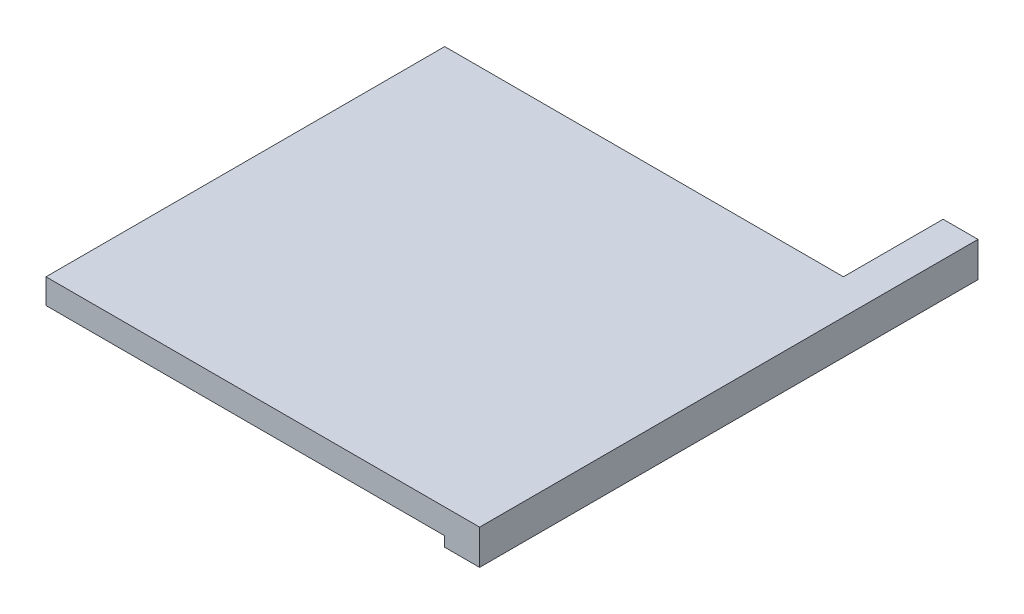
SolidWorks part; units mm, degrees
ref_plane "Front Plane" through (0, 0, 0) normal (0, 0, 1) x (1, 0, 0)
ref_plane "Top Plane" through (0, 0, 0) normal (0, 1, 0) x (1, 0, 0)
ref_plane "Right Plane" through (0, 0, 0) normal (1, 0, 0) x (0, 0, -1)
sketch "Sketch1" plane through (0, 0, 0) normal (0, 0, 1) x (1, 0, 0)
  line L1 (-3.5, -3.5) -> (3.5, -3.5)
  line L2 (-3.5, -3.5) -> (-3.5, 3.5)
  line L3 (-3.5, 3.5) -> (3.5, 3.5)
  line L4 (3.5, -3.5) -> (3.5, 3.5)
  line L5 (-3.5, -3.5) -> (3.5, 3.5) construction
  line L6 (-3.5, 3.5) -> (3.5, -3.5) construction
  point P0 (0, 0)
  dimension "D1" = 7
  dimension "D2" = 7
extrude "Boss-Extrude1" add sketch "Sketch1" along normal blind 100
sketch "Sketch3" plane through (0, 3.5, 0) normal (0, 1, 0) x (1, 0, 0)
  line L1 (-3.5, -100) -> (-83.5, -100)
  line L2 (-3.5, -100) -> (-3.5, -20)
  line L3 (-3.5, -20) -> (-83.5, -20)
  line L4 (-83.5, -100) -> (-83.5, -20)
extrude "Boss-Extrude2" add sketch "Sketch3" against normal blind 5
